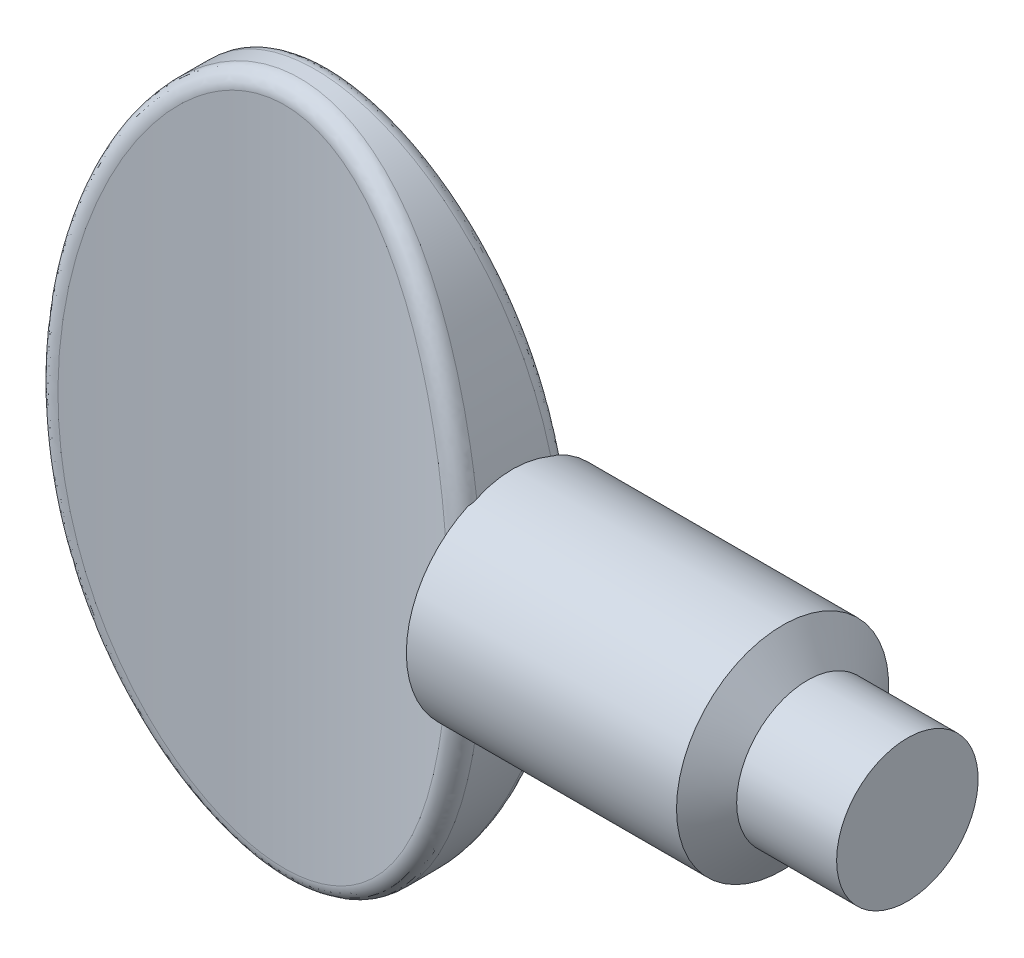
SolidWorks part; units mm, degrees
ref_plane "Front" through (0, 0, 0) normal (0, 0, 1) x (1, 0, 0)
ref_plane "Top" through (0, 0, 0) normal (0, 1, 0) x (1, 0, 0)
ref_plane "Right" through (0, 0, 0) normal (1, 0, 0) x (0, 0, -1)
ref_axis "Axis1" through (-50, 0, 0) along (1, 0, 0)
sketch "Sketch1" plane through (0, 0, 0) normal (0, 0, 1) x (1, 0, 0)
  line L0 (0, 0) -> (9.906, 0) construction
  line L1 (4.7413, -1.7526) -> (4.7413, 1.7526)
  line L2 (4.7413, -1.7526) -> (3.3847, -1.7526) construction
  ellipse E0 centre (0, 0) end of major axis (0, -5.715) minor radius 3.556
  dimension "D2" = 1.1853
  dimension "B" = 7.112
  dimension "L" = 6.35
extrude "Extrude1" add sketch "Sketch1" along normal mid plane 2.032
sketch "Sketch2" plane through (0, 0, 0) normal (0, 1, 0) x (1, 0, 0)
  line L0 (3.556, 1.016) -> (-3.556, 1.016) construction
  line L1 (0, 0) -> (0, 1.1721) construction
  line L2 (-1.7991, 0) -> (2.0444, 0) construction
  line L3 (-3.556, -1.016) -> (3.556, -1.016) construction
  line L6 (-3.556, 1.016) -> (-3.556, -1.016)
  line L7 (3.556, 1.016) -> (3.556, -1.016)
  arc A0 (-3.556, 1.016) -> (3.556, 1.016) centre (0, 10.6553) ccw
  arc A1 (-3.556, -1.016) -> (3.556, -1.016) centre (0, -10.6553) cw
extrude "Cut-Extrude1" cut sketch "Sketch2" against normal through all and the other way through all flip side to cut
fillet "Fillet3" radius 0.254 2 edges at (-3.4679, -1.2641, 0.984) (0.2073, 5.7053, -0.3831)
sketch "Sketch3" plane through (0, 0, 0) normal (0, 1, 0) x (1, 0, 0)
  line L0 (9.906, 0) -> (9.906, 1.1684)
  line L1 (0, 0) -> (21.0288, 0) construction
  line L2 (0, 0) -> (9.906, 0) construction
  line L3 (4.7413, 1.7526) -> (4.7413, 0) construction
  line L4 (4.7413, 1.7526) -> (7.8459, 1.7526)
  line L5 (9.906, 1.1684) -> (8.255, 1.1684)
  line L6 (4.7413, 1.7526) -> (3.3847, 1.7526)
  line L7 (2.5775, 0.7096) -> (2.5775, 0)
  line L8 (3.3847, 0) -> (3.3847, 1.7526) construction
  line L9 (2.5775, 0) -> (9.906, 0)
  line L10 (8.255, 1.1684) -> (7.8459, 1.7526)
  arc A0 (3.3847, 1.7526) -> (2.5775, 0.7096) centre (2.3072, 1.7526) cw
  arc A3 (-3.556, 1.016) -> (3.556, 1.016) centre (0, 10.6553) ccw construction
  dimension "D1" = 35
revolve "Revolve1" add sketch "Sketch3" angle 360 about L0
cosmetic thread "Cosmetic Thread1" [suppressed]
sketch "Sketch4" plane through (0, 0, 0) normal (0, 0, 1) x (1, 0, 0)
  line L0 (0, 0) -> (27.7993, 0) construction
  line L1 (7.6406, 1.7526) -> (7.8459, 1.397)
  line L2 (7.8459, 1.397) -> (8.0512, 1.7526)
  line L3 (8.0512, 1.7526) -> (8.0512, 2.1632)
  line L4 (8.0512, 2.1632) -> (7.6406, 2.1632)
  line L5 (7.6406, 2.1632) -> (7.6406, 1.7526)
  line L6 (7.8459, 1.7526) -> (7.8459, -1.7526) construction
  dimension "D1" = 2.794
  dimension "D2" = 3.5052
revolve "Cut-Revolve10" [suppressed] cut sketch "Sketch4" angle 360 about L0
pattern_linear "LPattern10" [suppressed] count 8 along (-1, 0, 0) of bodies 109
equation "\"D2@Sketch1\" = \"B@Sketch1\" / 6"
equation "\"D1@Fillet3\" = \"C1@Sketch2\" / 3"
equation "\"DIA@Sketch3\" = \"D@Sketch1\""
equation "\"D1@Cosmetic Thread1\" = \"L@Sketch1\" - \"Q@Sketch3\" -  ( \"D@Sketch1\" - \"P@Sketch3\" )  / 1.733"
equation "\"D1@Sketch4\" = \"D2@Cosmetic Thread1\""
equation "\"D2@Sketch4\" = \"DIA@Sketch3\""
equation "\"D1@LPattern10\" = \"D1@Cosmetic Thread1\" / \"P@LPattern10\" "
